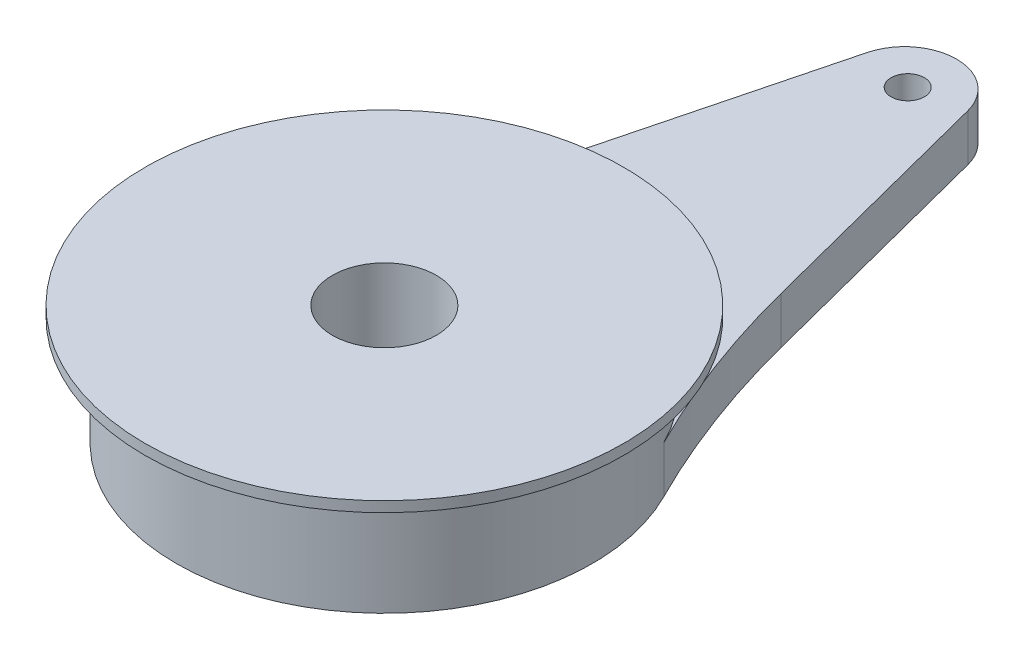
SolidWorks part; units mm, degrees
material "ABS"
ref_plane "前视基准面" through (0, 0, 0) normal (0, 0, 1) x (1, 0, 0)
ref_plane "上视基准面" through (0, 0, 0) normal (0, 1, 0) x (1, 0, 0)
ref_plane "右视基准面" through (0, 0, 0) normal (1, 0, 0) x (0, 0, -1)
sketch "Sketch1" plane through (0, 0, 0) normal (0, 1, 0) x (1, 0, 0)
  line L0 (-11.081, 27.0389) -> (-4.8418, 51.2478)
  line L1 (4.8418, 51.2478) -> (11.081, 27.0389)
  line L2 (0, 0) -> (0, 50.3054) construction
  circle A0 centre (0, 0) radius 20
  circle A2 centre (0, 0) radius 5
  arc A3 (-4.8418, 51.2478) -> (4.8418, 51.2478) centre (0, 50) cw
  arc A4 (-11.081, 27.0389) -> (-17.8606, 9) centre (-98.2331, 49.5) cw
  arc A5 (11.081, 27.0389) -> (17.8606, 9) centre (98.2331, 49.5) ccw
  dimension "D1" = 10
  dimension "D2" = 40
  dimension "D4" = 5
  dimension "D5" = 90
  dimension "D3" = 25
  dimension "D6" = 50
extrude "Boss-Extrude1" add sketch "Sketch1" along normal blind 4.5 contours A0 L2 A3 L0 A4 | L2 A0 A5 L1 A3 | A2 A0 region at (0, 0, -32.6468) region at (0, 0, -19.4343)
sketch "Sketch3" plane through (0, 0, 0) normal (0, 1, 0) x (1, 0, 0)
  circle A0 centre (0, 50.3054) radius 1.6
  dimension "D1" = 3.2
extrude "Cut-Extrude2" cut sketch "Sketch3" along normal up to next
extrude "Boss-Extrude2" add sketch "Sketch1<4>" along normal blind 10.5 contours A2 A0 region at (0, 0, -19.4343)
sketch "Sketch1<4>" plane through (0, 0, 0) normal (0, 1, 0) x (1, 0, 0) same geometry as "Sketch1"
sketch "Sketch4" plane through (0, 0, 0) normal (0, 1, 0) x (1, 0, 0)
  circle A0 centre (0, 0) radius 23
  circle A1 centre (0, 0) radius 20 construction
  circle A2 centre (0, 0) radius 5
  dimension "D1" = 3
  dimension "D2" = 10
extrude "Boss-Extrude3" add sketch "Sketch4" along normal blind 1 from surface starting at face at (0, 10.5, 20)
sketch "Sketch2" plane through (0, 0, 0) normal (0, 1, 0) x (1, 0, 0)
  circle A0 centre (0, 0) radius 13
  dimension "D1" = 26
extrude "Cut-Extrude1" cut sketch "Sketch2" along normal blind 4
